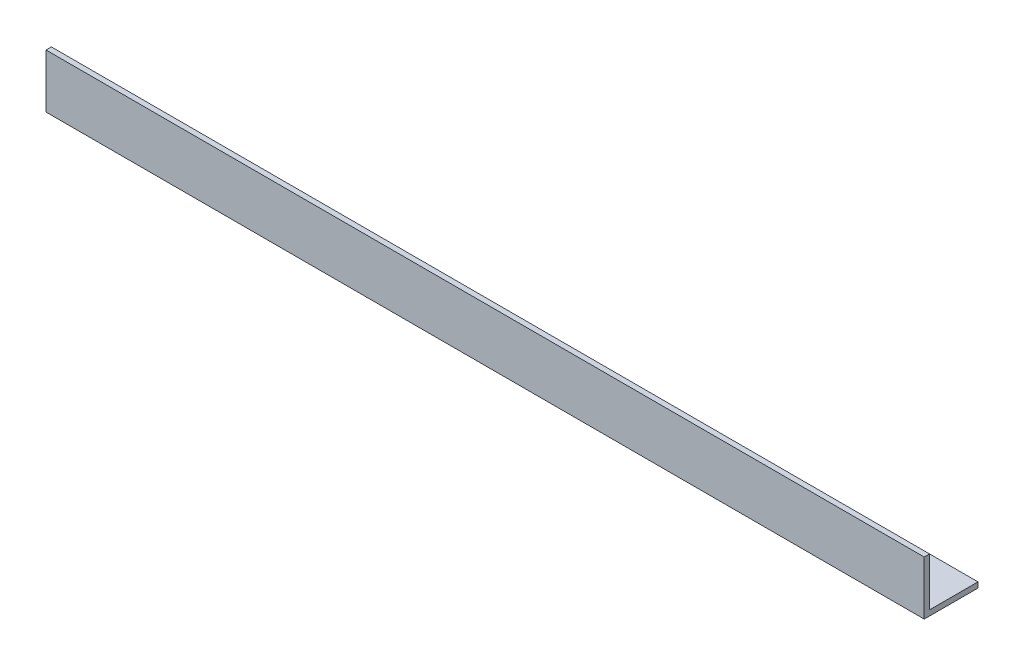
SolidWorks part; units mm, degrees
ref_plane "Спереди" through (0, 0, 0) normal (0, 0, 1) x (1, 0, 0)
ref_plane "Сверху" through (0, 0, 0) normal (0, 1, 0) x (1, 0, 0)
ref_plane "Справа" through (0, 0, 0) normal (1, 0, 0) x (0, 0, -1)
sketch "Эскиз1" plane through (0, 0, 0) normal (1, 0, 0) x (0, 0, -1)
  line L0 (0, 0) -> (30, 0)
  line L1 (0, 0) -> (0, 30)
extrude "Вытянуть-Тонкостенный1" add sketch "Эскиз1" along normal blind 490 thin thin type one direction wall 3
